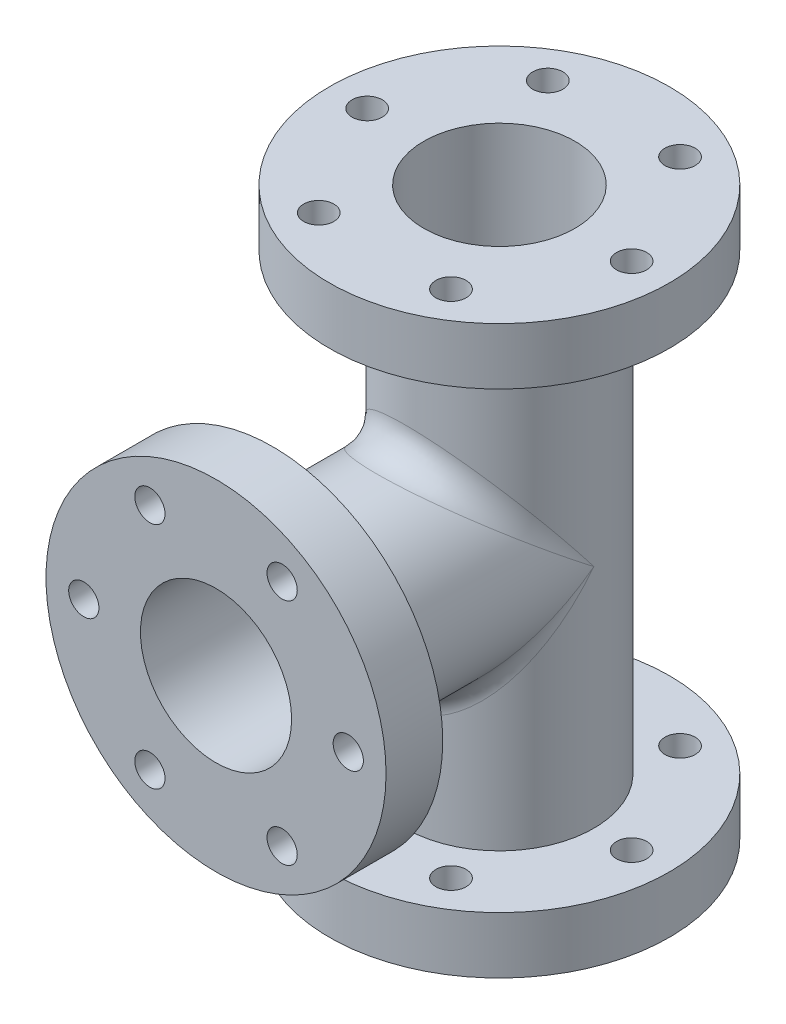
SolidWorks part; units mm, degrees
material "1023 Carbon Steel Sheet (SS)"
ref_plane "Front Plane" through (0, 0, 0) normal (0, 0, 1) x (1, 0, 0)
ref_plane "Top Plane" through (0, 0, 0) normal (0, 1, 0) x (1, 0, 0)
ref_plane "Right Plane" through (0, 0, 0) normal (1, 0, 0) x (0, 0, -1)
sketch "Sketch2" plane through (0, 0, 0) normal (0, 1, 0) x (1, 0, 0)
  circle A0 centre (0, 0) radius 50
  circle A1 centre (0, 0) radius 40
  dimension "D1" = 100
  dimension "D2" = 80
extrude "Boss-Extrude1" add sketch "Sketch2" along normal mid plane 300
sketch "Sketch3" plane through (0, -150, 0) normal (0, -1, 0) x (1, 0, 0)
  circle A0 centre (0, 0) radius 90
  circle A1 centre (0, 0) radius 50
  dimension "D1" = 180
  dimension "D2" = 100
extrude "Boss-Extrude2" add sketch "Sketch3" against normal blind 30
sketch "Sketch4" plane through (0, -150, 0) normal (0, -1, 0) x (1, 0, 0)
  line L0 (-90, 0) -> (90, 0) construction
  circle A0 centre (0, 0) radius 90 construction
  circle A1 centre (70, 0) radius 8
  circle A2 centre (35, -60.6218) radius 8
  circle A3 centre (-35, -60.6218) radius 8
  circle A4 centre (-70, 0) radius 8
  circle A5 centre (-35, 60.6218) radius 8
  circle A6 centre (35, 60.6218) radius 8
  point P7 (0, 0)
  point P22 (0, 0)
  dimension "D1" = 16
  dimension "D2" = 70
  dimension "D4" = 70
  dimension "D5" = 70
  dimension "D3" = 6
extrude "Cut-Extrude1" cut sketch "Sketch4" against normal through all
mirror "Mirror2" about plane through (0, 0, 0) normal (0, 1, 0) of "Cut-Extrude1", "Boss-Extrude2"
ref_plane "Plane1" through (0, 0, 150) normal (0, 0, 1) x (1, 0, 0)
sketch "Sketch5" plane through (0, 0, 150) normal (0, 0, 1) x (1, 0, 0)
  circle A0 centre (0, 0) radius 50
  dimension "D1" = 100
extrude "Boss-Extrude3" add sketch "Sketch5" against normal up to next
sketch "Sketch6" plane through (0, 0, 150) normal (0, 0, 1) x (1, 0, 0)
  circle A0 centre (0, 0) radius 40
  dimension "D1" = 80
extrude "Cut-Extrude2" cut sketch "Sketch6" against normal up to next
sketch "Sketch7" plane through (0, 0, 150) normal (0, 0, 1) x (1, 0, 0)
  circle A0 centre (0, 0) radius 90
  circle A1 centre (0, 0) radius 50
  dimension "D1" = 180
  dimension "D2" = 100
extrude "Boss-Extrude4" add sketch "Sketch7" against normal blind 30
sketch "Sketch8" plane through (0, 0, 150) normal (0, 0, 1) x (1, 0, 0)
  line L0 (-90, 0) -> (90, 0) construction
  circle A0 centre (0, 0) radius 90 construction
  circle A1 centre (70, 0) radius 8
  circle A2 centre (35, -60.6218) radius 8
  circle A3 centre (-35, -60.6218) radius 8
  circle A4 centre (-70, 0) radius 8
  circle A5 centre (-35, 60.6218) radius 8
  circle A6 centre (35, 60.6218) radius 8
  point P8 (0, 0)
  point P23 (0, 0)
  dimension "D1" = 16
  dimension "D4" = 70
  dimension "D5" = 70
  dimension "D2" = 70
  dimension "D3" = 6
extrude "Cut-Extrude3" cut sketch "Sketch8" against normal blind 40
fillet "Fillet1" radius 15 2 edges at (0, -50, 50) (0, 50, 50)
